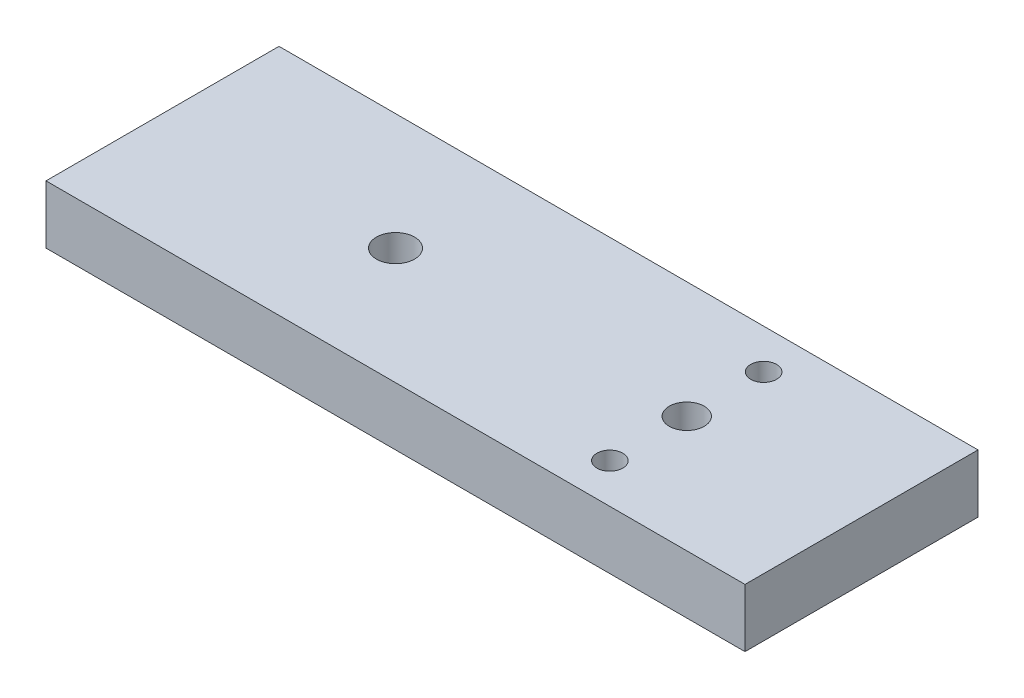
SolidWorks part; units mm, degrees
ref_plane "Front Plane" through (0, 0, 0) normal (0, 0, 1) x (1, 0, 0)
ref_plane "Top Plane" through (0, 0, 0) normal (0, 1, 0) x (1, 0, 0)
ref_plane "Right Plane" through (0, 0, 0) normal (1, 0, 0) x (0, 0, -1)
sketch "Sketch2" plane through (0, 0, 0) normal (0, 1, 0) x (1, 0, 0)
  line L0 (0, 12.7) -> (57.15, 12.7)
  line L1 (0, 0) -> (76.2, 0)
  line L2 (0, 0) -> (0, 25.4)
  line L3 (0, 25.4) -> (76.2, 25.4)
  line L4 (76.2, 0) -> (76.2, 25.4)
  line L5 (57.15, 12.7) -> (57.15, 21.082)
  line L6 (57.15, 12.7) -> (57.15, 4.318)
  circle A0 centre (57.15, 21.082) radius 1.4122
  circle A1 centre (57.15, 4.318) radius 1.4122
  circle A2 centre (57.15, 12.7) radius 1.905
  dimension "D1" = 76.2
  dimension "D2" = 25.4
  dimension "D3" = 57.15
extrude "Boss-Extrude1" add sketch "Sketch2" along normal blind 6.35 contours A2 A1 L2 L1 L4 L3 A0 region at (0.8032, 0, -19.05)
sketch "Sketch3" plane through (0, 6.35, 0) normal (0, 1, 0) x (1, 0, 0)
  line L0 (0, 25.4) -> (0, 12.7)
  line L1 (0, 25.4) -> (76.2, 25.4) construction
  line L2 (0, 0) -> (0, 25.4) construction
  line L3 (0, 12.7) -> (25.4, 12.7)
  circle A1 centre (25.4, 12.7) radius 2.0828
extrude "Cut-Extrude1" cut sketch "Sketch3" against normal blind 6.35 contours A1 region at (25.4, 6.35, -10.6761)
